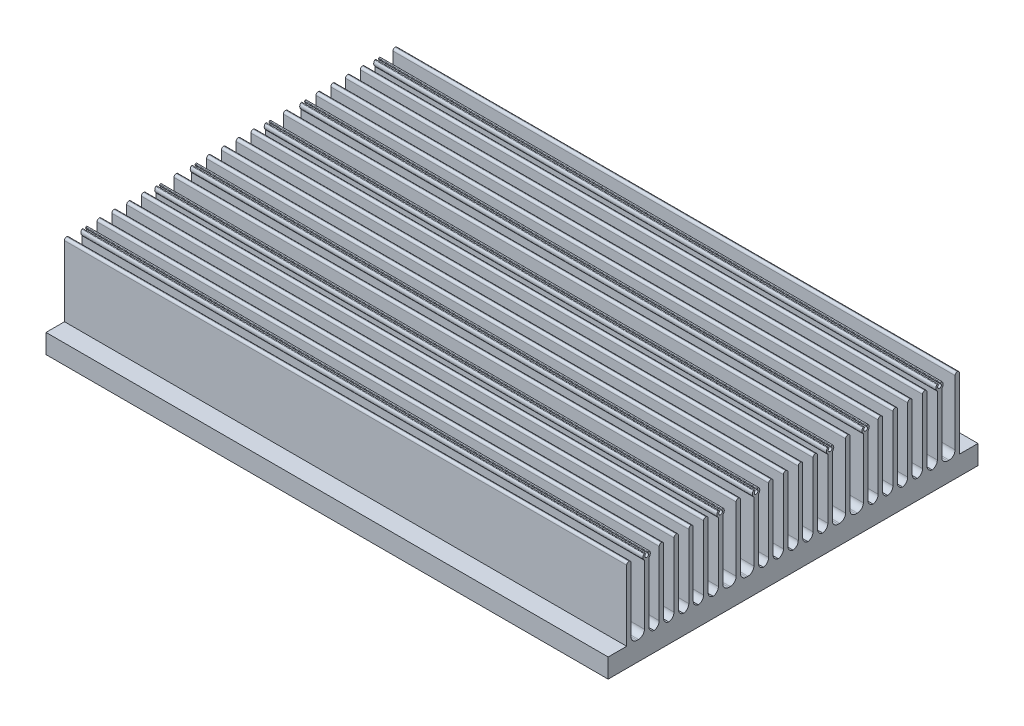
SolidWorks part; units mm, degrees
material "1060 Сплав"
ref_plane "Front" through (0, 0, 0) normal (0, 0, 1) x (1, 0, 0)
ref_plane "Top" through (0, 0, 0) normal (0, 1, 0) x (1, 0, 0)
ref_plane "Right" through (0, 0, 0) normal (1, 0, 0) x (0, 0, -1)
sketch "Эскиз1" plane through (0, 0, 0) normal (1, 0, 0) x (0, 0, -1)
  line L0 (0, 13) -> (0, 0)
  line L1 (0, 0) -> (250, 0)
  line L2 (250, 0) -> (250, 13)
  line L3 (0, 13) -> (12.5, 13)
  line L4 (14, 13) -> (14, 62) construction
  line L5 (26, 13) -> (26, 62) construction
  line L6 (14, 62) -> (12.5, 62)
  line L7 (12.5, 62) -> (12.5, 13)
  line L8 (74.5, 57.2639) -> (74.5, 13)
  line L9 (15.5, 13) -> (15.5, 62)
  line L10 (15.5, 62) -> (14, 62)
  line L11 (24.5, 57.2639) -> (24.5, 13)
  line L12 (24.5, 13) -> (15.5, 13)
  line L13 (27.5, 57.2639) -> (27.5, 13)
  line L14 (25.1615, 60.9524) -> (25.0318, 61.1771)
  line L15 (26.8385, 60.9524) -> (26.9682, 61.1771)
  line L16 (77.5, 57.2639) -> (77.5, 13)
  line L17 (75.1615, 60.9524) -> (75.0318, 61.1771)
  line L18 (76.8385, 60.9524) -> (76.9682, 61.1771)
  line L19 (76, 13) -> (76, 62) construction
  line L20 (148.5, 57.2639) -> (148.5, 13)
  line L21 (98.5, 57.2639) -> (98.5, 13)
  line L22 (101.5, 57.2639) -> (101.5, 13)
  line L23 (99.1615, 60.9524) -> (99.0318, 61.1771)
  line L24 (100.8385, 60.9524) -> (100.9682, 61.1771)
  line L25 (151.5, 57.2639) -> (151.5, 13)
  line L26 (149.1615, 60.9524) -> (149.0318, 61.1771)
  line L27 (150.8385, 60.9524) -> (150.9682, 61.1771)
  line L28 (100, 13) -> (100, 62) construction
  line L29 (150, 13) -> (150, 62) construction
  line L30 (222.5, 57.2639) -> (222.5, 13)
  line L31 (172.5, 57.2639) -> (172.5, 13)
  line L32 (175.5, 57.2639) -> (175.5, 13)
  line L33 (173.1615, 60.9524) -> (173.0318, 61.1771)
  line L34 (174.8385, 60.9524) -> (174.9682, 61.1771)
  line L35 (225.5, 57.2639) -> (225.5, 13)
  line L36 (223.1615, 60.9524) -> (223.0318, 61.1771)
  line L37 (224.8385, 60.9524) -> (224.9682, 61.1771)
  line L38 (174, 13) -> (174, 62) construction
  line L39 (224, 13) -> (224, 62) construction
  line L40 (37.5, 13) -> (37.5, 62)
  line L41 (34.5, 62) -> (34.5, 13)
  line L42 (36, 62) -> (34.5, 62)
  line L43 (37.5, 62) -> (36, 62)
  line L44 (47.5, 13) -> (47.5, 62)
  line L45 (44.5, 62) -> (44.5, 13)
  line L46 (46, 62) -> (44.5, 62)
  line L47 (47.5, 62) -> (46, 62)
  line L48 (57.5, 13) -> (57.5, 62)
  line L49 (54.5, 62) -> (54.5, 13)
  line L50 (56, 62) -> (54.5, 62)
  line L51 (57.5, 62) -> (56, 62)
  line L52 (67.5, 13) -> (67.5, 62)
  line L53 (64.5, 62) -> (64.5, 13)
  line L54 (66, 62) -> (64.5, 62)
  line L55 (67.5, 62) -> (66, 62)
  line L56 (89.5, 13) -> (89.5, 62)
  line L57 (86.5, 62) -> (86.5, 13)
  line L58 (88, 62) -> (86.5, 62)
  line L59 (89.5, 62) -> (88, 62)
  line L60 (111.5, 13) -> (111.5, 62)
  line L61 (108.5, 62) -> (108.5, 13)
  line L62 (110, 62) -> (108.5, 62)
  line L63 (111.5, 62) -> (110, 62)
  line L64 (121.5, 13) -> (121.5, 62)
  line L65 (118.5, 62) -> (118.5, 13)
  line L66 (120, 62) -> (118.5, 62)
  line L67 (121.5, 62) -> (120, 62)
  line L68 (131.5, 13) -> (131.5, 62)
  line L69 (128.5, 62) -> (128.5, 13)
  line L70 (130, 62) -> (128.5, 62)
  line L71 (131.5, 62) -> (130, 62)
  line L72 (141.5, 13) -> (141.5, 62)
  line L73 (138.5, 62) -> (138.5, 13)
  line L74 (140, 62) -> (138.5, 62)
  line L75 (141.5, 62) -> (140, 62)
  line L76 (163.5, 13) -> (163.5, 62)
  line L77 (160.5, 62) -> (160.5, 13)
  line L78 (162, 62) -> (160.5, 62)
  line L79 (163.5, 62) -> (162, 62)
  line L80 (185.5, 13) -> (185.5, 62)
  line L81 (182.5, 62) -> (182.5, 13)
  line L82 (184, 62) -> (182.5, 62)
  line L83 (185.5, 62) -> (184, 62)
  line L84 (195.5, 13) -> (195.5, 62)
  line L85 (192.5, 62) -> (192.5, 13)
  line L86 (194, 62) -> (192.5, 62)
  line L87 (195.5, 62) -> (194, 62)
  line L88 (205.5, 13) -> (205.5, 62)
  line L89 (202.5, 62) -> (202.5, 13)
  line L90 (204, 62) -> (202.5, 62)
  line L91 (205.5, 62) -> (204, 62)
  line L92 (215.5, 13) -> (215.5, 62)
  line L93 (212.5, 62) -> (212.5, 13)
  line L94 (214, 62) -> (212.5, 62)
  line L95 (215.5, 62) -> (214, 62)
  line L96 (237.5, 13) -> (237.5, 62)
  line L97 (234.5, 62) -> (234.5, 13)
  line L98 (236, 62) -> (234.5, 62)
  line L99 (237.5, 62) -> (236, 62)
  line L100 (27.5, 13) -> (34.5, 13)
  line L101 (37.5, 13) -> (44.5, 13)
  line L102 (47.5, 13) -> (54.5, 13)
  line L103 (57.5, 13) -> (64.5, 13)
  line L104 (237.5, 13) -> (250, 13)
  line L105 (225.5, 13) -> (234.5, 13)
  line L106 (215.5, 13) -> (222.5, 13)
  line L107 (205.5, 13) -> (212.5, 13)
  line L108 (195.5, 13) -> (202.5, 13)
  line L109 (175.5, 13) -> (192.5, 13)
  line L110 (163.5, 13) -> (172.5, 13)
  line L111 (151.5, 13) -> (160.5, 13)
  line L112 (141.5, 13) -> (148.5, 13)
  line L113 (131.5, 13) -> (138.5, 13)
  line L114 (121.5, 13) -> (128.5, 13)
  line L115 (111.5, 13) -> (118.5, 13)
  line L116 (101.5, 13) -> (108.5, 13)
  line L117 (89.5, 13) -> (98.5, 13)
  line L118 (77.5, 13) -> (86.5, 13)
  line L119 (67.5, 13) -> (74.5, 13)
  arc A0 (24.2484, 61.2838) -> (24.3333, 57.6366) centre (26, 59.5) ccw
  arc A1 (25.0918, 60.3588) -> (26.9082, 60.3588) centre (26, 59.5) ccw
  arc A2 (27.6667, 57.6366) -> (27.7516, 61.2838) centre (26, 59.5) ccw
  arc A3 (27.6667, 57.6366) -> (27.5, 57.2639) centre (28, 57.2639) ccw
  arc A4 (24.5, 57.2639) -> (24.3333, 57.6366) centre (24, 57.2639) ccw
  arc A5 (27.7516, 61.2838) -> (26.9682, 61.1771) centre (27.4013, 60.9271) ccw
  arc A6 (26.9082, 60.3588) -> (26.8385, 60.9524) centre (27.2715, 60.7024) cw
  arc A7 (25.0918, 60.3588) -> (25.1615, 60.9524) centre (24.7285, 60.7024) ccw
  arc A8 (25.0318, 61.1771) -> (24.2484, 61.2838) centre (24.5987, 60.9271) ccw
  arc A9 (74.2484, 61.2838) -> (74.3333, 57.6366) centre (76, 59.5) ccw
  arc A10 (75.0918, 60.3588) -> (76.9082, 60.3588) centre (76, 59.5) ccw
  arc A11 (77.6667, 57.6366) -> (77.7516, 61.2838) centre (76, 59.5) ccw
  arc A12 (77.6667, 57.6366) -> (77.5, 57.2639) centre (78, 57.2639) ccw
  arc A13 (74.5, 57.2639) -> (74.3333, 57.6366) centre (74, 57.2639) ccw
  arc A14 (77.7516, 61.2838) -> (76.9682, 61.1771) centre (77.4013, 60.9271) ccw
  arc A15 (76.9082, 60.3588) -> (76.8385, 60.9524) centre (77.2715, 60.7024) cw
  arc A16 (75.0918, 60.3588) -> (75.1615, 60.9524) centre (74.7285, 60.7024) ccw
  arc A17 (75.0318, 61.1771) -> (74.2484, 61.2838) centre (74.5987, 60.9271) ccw
  arc A18 (98.2484, 61.2838) -> (98.3333, 57.6366) centre (100, 59.5) ccw
  arc A19 (99.0918, 60.3588) -> (100.9082, 60.3588) centre (100, 59.5) ccw
  arc A20 (101.6667, 57.6366) -> (101.7516, 61.2838) centre (100, 59.5) ccw
  arc A21 (101.6667, 57.6366) -> (101.5, 57.2639) centre (102, 57.2639) ccw
  arc A22 (98.5, 57.2639) -> (98.3333, 57.6366) centre (98, 57.2639) ccw
  arc A23 (101.7516, 61.2838) -> (100.9682, 61.1771) centre (101.4013, 60.9271) ccw
  arc A24 (100.9082, 60.3588) -> (100.8385, 60.9524) centre (101.2715, 60.7024) cw
  arc A25 (99.0918, 60.3588) -> (99.1615, 60.9524) centre (98.7285, 60.7024) ccw
  arc A26 (99.0318, 61.1771) -> (98.2484, 61.2838) centre (98.5987, 60.9271) ccw
  arc A27 (148.2484, 61.2838) -> (148.3333, 57.6366) centre (150, 59.5) ccw
  arc A28 (149.0918, 60.3588) -> (150.9082, 60.3588) centre (150, 59.5) ccw
  arc A29 (151.6667, 57.6366) -> (151.7516, 61.2838) centre (150, 59.5) ccw
  arc A30 (151.6667, 57.6366) -> (151.5, 57.2639) centre (152, 57.2639) ccw
  arc A31 (148.5, 57.2639) -> (148.3333, 57.6366) centre (148, 57.2639) ccw
  arc A32 (151.7516, 61.2838) -> (150.9682, 61.1771) centre (151.4013, 60.9271) ccw
  arc A33 (150.9082, 60.3588) -> (150.8385, 60.9524) centre (151.2715, 60.7024) cw
  arc A34 (149.0918, 60.3588) -> (149.1615, 60.9524) centre (148.7285, 60.7024) ccw
  arc A35 (149.0318, 61.1771) -> (148.2484, 61.2838) centre (148.5987, 60.9271) ccw
  arc A36 (172.2484, 61.2838) -> (172.3333, 57.6366) centre (174, 59.5) ccw
  arc A37 (173.0918, 60.3588) -> (174.9082, 60.3588) centre (174, 59.5) ccw
  arc A38 (175.6667, 57.6366) -> (175.7516, 61.2838) centre (174, 59.5) ccw
  arc A39 (175.6667, 57.6366) -> (175.5, 57.2639) centre (176, 57.2639) ccw
  arc A40 (172.5, 57.2639) -> (172.3333, 57.6366) centre (172, 57.2639) ccw
  arc A41 (175.7516, 61.2838) -> (174.9682, 61.1771) centre (175.4013, 60.9271) ccw
  arc A42 (174.9082, 60.3588) -> (174.8385, 60.9524) centre (175.2715, 60.7024) cw
  arc A43 (173.0918, 60.3588) -> (173.1615, 60.9524) centre (172.7285, 60.7024) ccw
  arc A44 (173.0318, 61.1771) -> (172.2484, 61.2838) centre (172.5987, 60.9271) ccw
  arc A45 (222.2484, 61.2838) -> (222.3333, 57.6366) centre (224, 59.5) ccw
  arc A46 (223.0918, 60.3588) -> (224.9082, 60.3588) centre (224, 59.5) ccw
  arc A47 (225.6667, 57.6366) -> (225.7516, 61.2838) centre (224, 59.5) ccw
  arc A48 (225.6667, 57.6366) -> (225.5, 57.2639) centre (226, 57.2639) ccw
  arc A49 (222.5, 57.2639) -> (222.3333, 57.6366) centre (222, 57.2639) ccw
  arc A50 (225.7516, 61.2838) -> (224.9682, 61.1771) centre (225.4013, 60.9271) ccw
  arc A51 (224.9082, 60.3588) -> (224.8385, 60.9524) centre (225.2715, 60.7024) cw
  arc A52 (223.0918, 60.3588) -> (223.1615, 60.9524) centre (222.7285, 60.7024) ccw
  arc A53 (223.0318, 61.1771) -> (222.2484, 61.2838) centre (222.5987, 60.9271) ccw
  point P20 (26, 62)
  point P46 (76, 62)
  point P70 (100, 62)
  point P94 (150, 62)
  point P118 (174, 62)
  point P142 (224, 62)
  dimension "D8" = 5
  dimension "D10" = 2.5
  dimension "D9" = 0.5
  dimension "D1" = 13
  dimension "D2" = 250
  dimension "D3" = 49
  dimension "D4" = 14
  dimension "D5" = 12
  dimension "D6" = 3
  dimension "D7" = 1.5
  dimension "D11" = 30
  dimension "D12" = 30
  dimension "D13" = 2
  dimension "D14" = 3
  dimension "D15" = 2
  dimension "D16" = 4
  dimension "D17" = 2
  dimension "D18" = 3
extrude "Бобышка-Вытянуть1" add sketch "Эскиз1" along normal blind 380 contours L36 A53 A45 A49 L30 L106 L92 L95 L94 L93 L107 L88 L91 L90 L89 L108 L84 L87 L86 L85 L109 L32 A39 A38 A41 L34 A42 A37 A43 L33 A44 A36 A40 L31 L110 L76 L79 L78 L77 L111 L25 A30 A29 A32 L27 A33 A28 A34 L26 | L81 L109 L80 L83 L82 region at (0, 10.4243, -6.25) region at (0, 37.5, -184)
fillet "Скругление1" radius 1.5 32 edges at (190, 62, -234.5) (190, 62, -237.5) (190, 62, -12.5) (190, 62, -15.5) (190, 62, -34.5) (190, 62, -37.5) (190, 62, -44.5) (190, 62, -47.5) (190, 62, -54.5) (190, 62, -57.5) (190, 62, -64.5) (190, 62, -67.5) (190, 62, -86.5) (190, 62, -89.5) (190, 62, -108.5) (190, 62, -111.5) (190, 62, -118.5) (190, 62, -121.5) (190, 62, -128.5) (190, 62, -131.5) (190, 62, -138.5) (190, 62, -141.5) (190, 62, -160.5) (190, 62, -163.5) (190, 62, -182.5) (190, 62, -185.5) (190, 62, -192.5) (190, 62, -195.5) (190, 62, -202.5) (190, 62, -205.5) (190, 62, -212.5) (190, 62, -215.5)
fillet "Скругление2" radius 4 42 edges at (190, 13, -234.5) (190, 13, -225.5) (190, 13, -15.5) (190, 13, -24.5) (190, 13, -27.5) (190, 13, -34.5) (190, 13, -37.5) (190, 13, -44.5) (190, 13, -47.5) (190, 13, -54.5) (190, 13, -57.5) (190, 13, -64.5) (190, 13, -67.5) (190, 13, -74.5) (190, 13, -77.5) (190, 13, -86.5) (190, 13, -89.5) (190, 13, -98.5) (190, 13, -101.5) (190, 13, -108.5) (190, 13, -111.5) (190, 13, -118.5) (190, 13, -121.5) (190, 13, -128.5) (190, 13, -131.5) (190, 13, -138.5) (190, 13, -141.5) (190, 13, -148.5) (190, 13, -151.5) (190, 13, -160.5) (190, 13, -163.5) (190, 13, -172.5) (190, 13, -175.5) (190, 13, -182.5) (190, 13, -185.5) (190, 13, -192.5) (190, 13, -195.5) (190, 13, -202.5) (190, 13, -205.5) (190, 13, -212.5) (190, 13, -215.5) (190, 13, -222.5)
